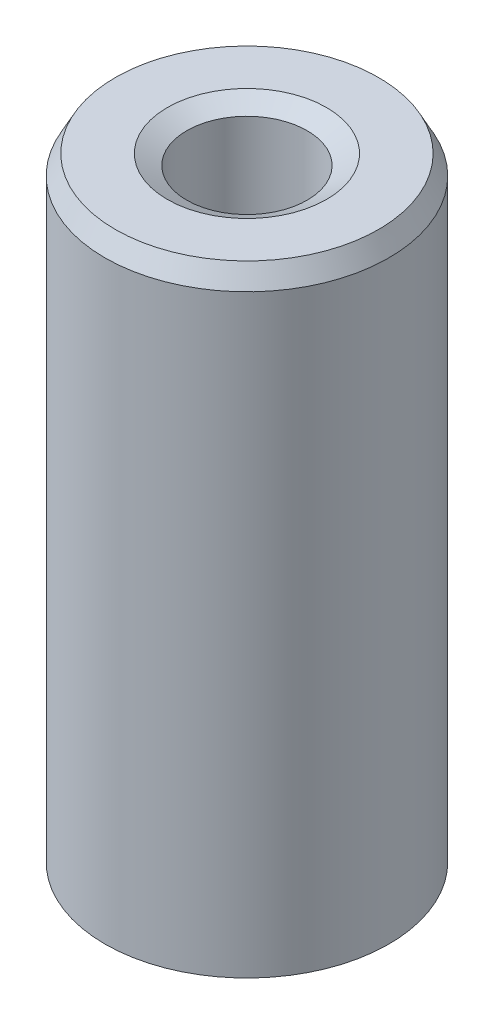
SolidWorks part; units mm, degrees
ref_plane "Front Plane" through (0, 0, 0) normal (0, 0, 1) x (1, 0, 0)
ref_plane "Top Plane" through (0, 0, 0) normal (0, 1, 0) x (1, 0, 0)
ref_plane "Right Plane" through (0, 0, 0) normal (1, 0, 0) x (0, 0, -1)
sketch "Sketch1" plane through (0, 0, 0) normal (0, 1, 0) x (1, 0, 0)
  circle A0 centre (0, 0) radius 7.5
  dimension "SLEEVE_OD" = 15
extrude "Boss-Extrude1" add sketch "Sketch1" along normal blind 32.9642
sketch "Sketch2" plane through (0, 0, 0) normal (0, 1, 0) x (1, 0, 0)
  circle A0 centre (0, 0) radius 3.1817
  dimension "BORE_D" = 6.3633
extrude "Cut-Extrude1" cut sketch "Sketch2" along normal through all
chamfer "Chamfer1" distance 1.0252 angle 28.03 4 edges at (0, 32.9642, 3.1817) (0, 0, 3.1817) (0, 0, 7.5) (0, 32.9642, 7.5) first distance on face at (0, 32.9642, 3.1817) first distance on face at (0, 0, 3.1817) first distance on face at (0, 32.9642, 7.5)
